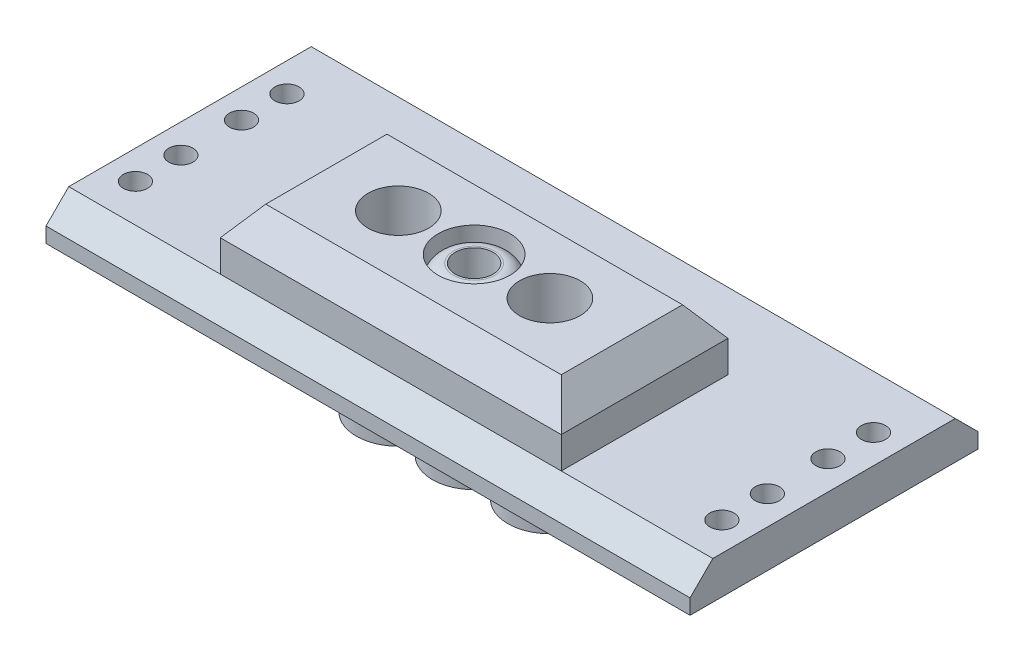
SolidWorks part; units mm, degrees
ref_plane "Alzado" through (0, 0, 0) normal (0, 0, 1) x (1, 0, 0)
ref_plane "Planta" through (0, 0, 0) normal (0, 1, 0) x (1, 0, 0)
ref_plane "Vista lateral" through (0, 0, 0) normal (1, 0, 0) x (0, 0, -1)
sketch "Croquis1" plane through (0, 0, 0) normal (0, 1, 0) x (1, 0, 0)
  line L0 (38.7, -5) -> (38.7, -11) construction
  line L1 (-42.5, -19) -> (42.5, -19)
  line L2 (-42.5, -19) -> (-42.5, 19)
  line L3 (-42.5, 19) -> (42.5, 19)
  line L4 (42.5, -19) -> (42.5, 19)
  line L5 (-42.5, -19) -> (42.5, 19) construction
  line L6 (-42.5, 19) -> (42.5, -19) construction
  line L7 (38.7, -11) -> (-38.7, -11) construction
  line L8 (-38.7, -5) -> (-38.7, -11) construction
  line L9 (38.7, 9) -> (38.7, 3) construction
  line L10 (38.7, 9) -> (38.7, 19) construction
  line L11 (38.7, 9) -> (42.5, 9) construction
  line L12 (-38.7, 9) -> (-38.7, 3) construction
  line L13 (-38.7, 9) -> (-38.7, 19) construction
  line L14 (0, 0) -> (0, -5) construction
  line L15 (-10, -5) -> (10, -5) construction
  circle A0 centre (38.7, -11) radius 1.6
  circle A1 centre (38.7, -5) radius 1.6
  circle A2 centre (-38.7, -11) radius 1.6
  circle A3 centre (-38.7, -5) radius 1.6
  circle A4 centre (38.7, 9) radius 1.6
  circle A5 centre (38.7, 3) radius 1.6
  circle A6 centre (-38.7, 3) radius 1.6
  circle A7 centre (-38.7, 9) radius 1.6
  circle A8 centre (0, -5) radius 2.5
  circle A9 centre (10, -5) radius 2.55
  circle A10 centre (-10, -5) radius 2.55
  point P0 (0, 0)
  point P31 (0, -5)
  dimension "D4" = 3.2
  dimension "D5" = 3.2
  dimension "D6" = 3.2
  dimension "D7" = 3.2
  dimension "D13" = 3.2
  dimension "D14" = 3.2
  dimension "D20" = 3.2
  dimension "D21" = 3.2
  dimension "D22" = 5
  dimension "D24" = 5.1
  dimension "D25" = 5.1
  dimension "D1" = 85
  dimension "D2" = 38
  dimension "D3" = 6
  dimension "D8" = 6
  dimension "D9" = 3.8
  dimension "D10" = 8
  dimension "D11" = 3.8
  dimension "D12" = 6
  dimension "D15" = 3.8
  dimension "D16" = 10
  dimension "D17" = 6
  dimension "D18" = 10
  dimension "D19" = 3.8
  dimension "D23" = 14
  dimension "D26" = 10
extrude "Saliente-Extruir1" add sketch "Croquis1" along normal blind 5
sketch "Croquis2" plane through (0, 5, 0) normal (0, 1, 0) x (1, 0, 0)
  line L0 (-42.5, -19) -> (42.5, -19) construction
  line L1 (0, -5) -> (0, 0) construction
  circle A0 centre (0, -5) radius 4.75
  circle A1 centre (0, -5) radius 2.5
  dimension "D2" = 9.5
  dimension "D3" = 5
  dimension "D1" = 14
extrude "Saliente-Extruir2" add sketch "Croquis2" along normal blind 7
fillet "Redondeo2" radius 2 1 edges at (0, 12, 9.75)
sketch "Croquis4" plane through (0, 5, 0) normal (0, 1, 0) x (1, 0, 0)
  line L0 (0, -5) -> (-10, -5) construction
  line L1 (0, -5) -> (10, -5) construction
  circle A0 centre (10, -5) radius 2.55
  circle A1 centre (-10, -5) radius 2.55
  circle A2 centre (-10, -5) radius 4
  circle A3 centre (10, -5) radius 4
  dimension "D1" = 5.1
  dimension "D2" = 5.1
  dimension "D5" = 8
  dimension "D6" = 8
  dimension "D3" = 10
  dimension "D4" = 10
extrude "Saliente-Extruir3" add sketch "Croquis4" along normal blind 3
fillet "Redondeo3" radius 2 2 edges at (-10, 8, 9) (10, 8, 9)
chamfer "Chaflán1" distance 3 angle 45 2 edges at (0, 5, -19) (0, 5, 19)
sketch "Croquis5" plane through (0, 5, 0) normal (0, 1, 0) x (1, 0, 0)
  line L1 (-22.5, 6) -> (22.5, 6)
  line L2 (-22.5, 6) -> (-22.5, -16)
  line L3 (-22.5, -16) -> (22.5, -16)
  line L4 (22.5, 6) -> (22.5, -16)
  line L5 (-22.5, 6) -> (22.5, -16) construction
  line L6 (-22.5, -16) -> (22.5, 6) construction
  line L7 (-16.5, 2) -> (16.5, 2)
  line L8 (-16.5, 2) -> (-16.5, -12)
  line L9 (-16.5, -12) -> (16.5, -12)
  line L10 (16.5, 2) -> (16.5, -12)
  line L11 (-16.5, 2) -> (16.5, -12) construction
  line L12 (-16.5, -12) -> (16.5, 2) construction
  point P0 (0, -5)
  point P6 (0, -5)
  circle M7 centre (-10, -5) radius 4
  circle M20 centre (0, -5) radius 4.75
  circle M21 centre (10, -5) radius 4
  dimension "D1" = 45
  dimension "D2" = 22
  dimension "D3" = 6
  dimension "D4" = 4
extrude "Saliente-Extruir4" add sketch "Croquis5" along normal blind 8 separate body contours L4 L1 L2 L3 L7 L10 L9 L8 | L8 L9 L7 M20 M7 | L10 L7 L9 M20 M21 region at (0, 5, -5.4991) region at (0, 5, -1.6415)
sketch "Croquis9" plane through (0, 0, 0) normal (0, -1, 0) x (1, 0, 0)
  line L0 (0, -55) -> (0, 55) construction
  circle A0 centre (0, 5) radius 5.5
  circle A1 centre (0, 5) radius 2.5 construction
  circle A2 centre (10, 5) radius 5.55
  circle A3 centre (10, 5) radius 2.55 construction
  circle A4 centre (-10, 5) radius 5.55
  circle M1 centre (10, 5) radius 2.55
  circle M14 centre (0, 5) radius 2.5
  circle M15 centre (-10, 5) radius 2.55
  dimension "D1" = 3
  dimension "D2" = 3
extrude "Saliente-Extruir7" add sketch "Croquis9" along normal blind 10 contours A0 A2 M1 | A0 A4 A2 M14 | A4 A0 M15 | A0 A2 | A4 A0 region at (4.9745, 0, 5) region at (5.5161, 0, 6.2381) region at (4.3017, 0, 5) region at (-4.9745, 0, 5) region at (-5.6533, 0, 5)
chamfer "Chaflán2" distance 3 angle 52 4 edges at (22.5, 13, 5) (-22.5, 13, 5) (0, 13, -6) (0, 13, 16) first distance on face at (0, 13, 5)
